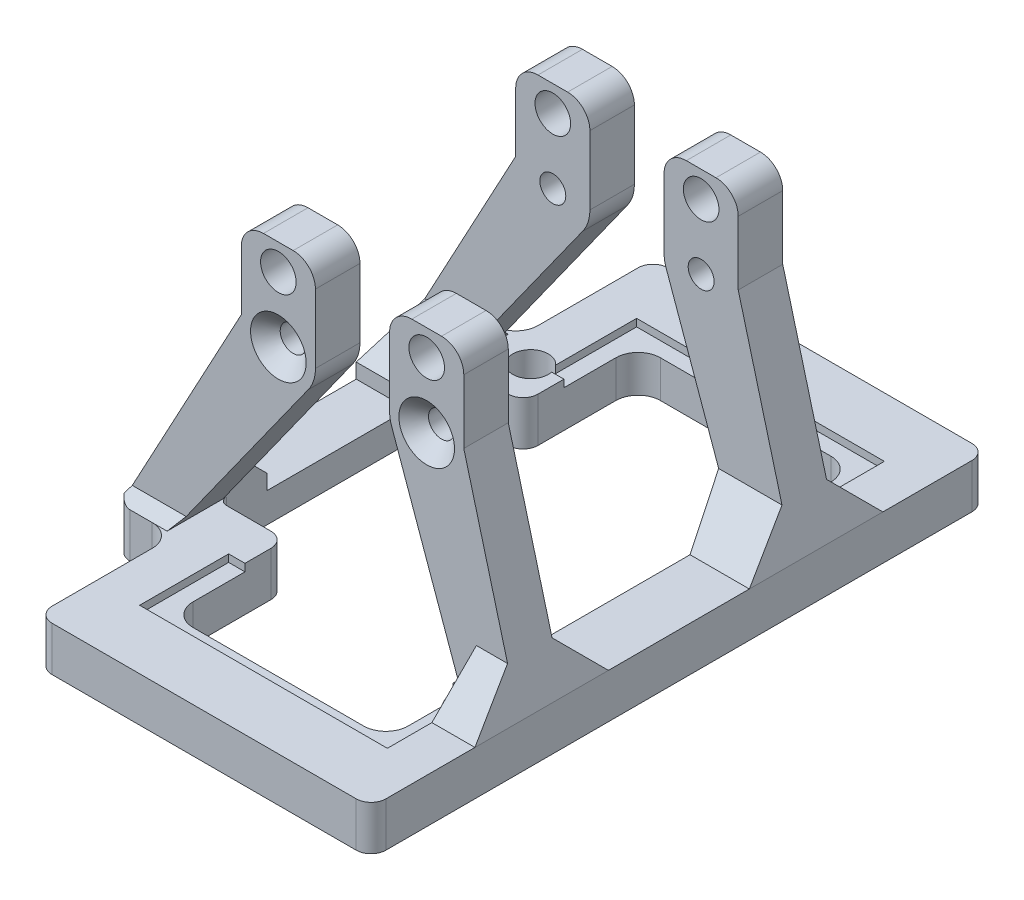
SolidWorks part; units mm, degrees
ref_plane "前视基准面" through (0, 0, 0) normal (0, 0, 1) x (1, 0, 0)
ref_plane "上视基准面" through (0, 0, 0) normal (0, 1, 0) x (1, 0, 0)
ref_plane "右视基准面" through (0, 0, 0) normal (1, 0, 0) x (0, 0, -1)
other "Configuration Table"
sketch "草图1" plane through (0, 0, 0) normal (0, 1, 0) x (1, 0, 0)
  line L0 (0, -76) -> (0, -106)
  line L1 (0, 0) -> (45, 0)
  line L2 (0, 0) -> (0, -30)
  line L3 (0, -106) -> (45, -106)
  line L4 (45, 0) -> (45, -106)
  line L5 (8, -21.5) -> (37, -21.5)
  line L6 (8, -21.5) -> (8, -37)
  line L7 (8, -84.5) -> (37, -84.5)
  line L8 (37, -21.5) -> (37, -84.5)
  line L9 (0, -30) -> (-8, -30)
  line L11 (0, -76) -> (-8, -76)
  line L12 (-8, -30) -> (-8, -76)
  line L13 (8, -69) -> (8, -84.5)
  line L14 (8, -37) -> (-1, -37)
  line L16 (8, -69) -> (-1, -69)
  line L17 (-1, -37) -> (-1, -69)
  circle A0 centre (4, -32) radius 1.75
  circle A1 centre (41, -74) radius 1.75
  dimension "D8" = 3.5
  dimension "D12" = 3.5
  dimension "D13" = 8
  dimension "D1" = 106
  dimension "D2" = 45
  dimension "D3" = 21.5
  dimension "D4" = 21.5
  dimension "D5" = 8
  dimension "D6" = 8
  dimension "D7" = 32
  dimension "D9" = 74
  dimension "D10" = 4
  dimension "D11" = 4
  dimension "D14" = 30
  dimension "D15" = 30
  dimension "D16" = 7
  dimension "D17" = 7
  dimension "D18" = 7
extrude "凸台-拉伸1" add sketch "草图1" along normal blind 6
sketch "草图3" plane through (0, 6, 0) normal (0, 1, 0) x (1, 0, 0)
  line L0 (45, -106) -> (45, 0) construction
  line L1 (0, -106) -> (45, -106)
  line L2 (0, -106) -> (0, -94.5)
  line L3 (0, -94.5) -> (45, -94.5)
  line L4 (45, -106) -> (45, -94.5)
  line L5 (37, -21.5) -> (8, -21.5) construction
  line L6 (0, 0) -> (45, 0)
  line L7 (0, 0) -> (0, -11.5)
  line L8 (0, -11.5) -> (45, -11.5)
  line L9 (45, 0) -> (45, -11.5)
  line L10 (8, -84.5) -> (37, -84.5) construction
  dimension "D1" = 10
  dimension "0" = 10
extrude "切除-拉伸1" cut sketch "草图3" against normal blind 10
sketch "草图4" plane through (0, 6, 0) normal (0, 1, 0) x (1, 0, 0)
  line L0 (45, -71) -> (45, -77)
  line L1 (45, -94.5) -> (45, -11.5) construction
  arc A0 (45, -71) -> (45, -77) centre (41, -74) ccw
  circle A1 centre (41, -74) radius 1.75
  dimension "D1" = 10
extrude "凸台-拉伸3" add sketch "草图4" against normal blind 6
sketch "草图13" plane through (0, 6, 0) normal (0, 1, 0) x (1, 0, 0)
  circle A0 centre (41, -74) radius 1.75
extrude "凸台-拉伸6" add sketch "草图13" against normal blind 0.5
sketch "草图14" plane through (0, 0, 0) normal (0, -1, 0) x (-1, 0, 0)
  circle A0 centre (-41, -74) radius 2.4
  dimension "D1" = 4.8
extrude "切除-拉伸8" cut sketch "草图14" against normal blind 4.5
sketch "草图15" plane through (0, 6, 0) normal (0, 1, 0) x (1, 0, 0)
  circle A0 centre (4, -32) radius 2.4
  dimension "D1" = 4.8
extrude "切除-拉伸9" cut sketch "草图15" against normal blind 4.5
ref_plane "基准面1" through (0, 0, 68.5) normal (0, 0, 1) x (1, 0, 0)
sketch "草图5" plane through (0, 0, 68.5) normal (0, 0, 1) x (1, 0, 0)
  line L0 (45, 6) -> (37.5, 34.1545)
  line L1 (37, 6) -> (27.8572, 31.6442)
  line L3 (-8, 6) -> (7.5, 34.7615)
  line L4 (-1, 6) -> (16.5, 30.5)
  line L5 (13.5784, 30.5) -> (17.5, 30.5) construction
  line L6 (-8, 6) -> (-1, 6)
  line L7 (37, 6) -> (45, 6)
  line L8 (37.5, 48.5) -> (37.5, 30.9) construction
  line L14 (27.5, 33.5) -> (27.5, 45.7615)
  line L15 (27.5, 45.7615) -> (37.5, 45.7615)
  line L16 (37.5, 34.1453) -> (37.5, 45.7615)
  line L17 (17.5, 23.9) -> (17.5, 48.5) construction
  line L19 (7.5, 34.7615) -> (7.5, 45.7615)
  line L20 (7.5, 45.7615) -> (17.5, 45.7615)
  line L21 (17.5, 33.5) -> (17.5, 45.7615)
  arc A0 (27.5, 33.5) -> (27.8572, 31.6442) centre (32.5, 33.5) ccw
  arc A2 (16.5, 30.5) -> (17.5, 33.5) centre (12.5, 33.5) ccw
  dimension "D1" = 11
  dimension "D2" = 10
  dimension "D3" = 0
extrude "凸台-拉伸4" add sketch "草图5" along normal blind 6 and the other way blind 37 contours L3 L6 L4 | A0 L1 L7 L0 | L0 A0 L1 region at (35.2194, 26.634, 68.5) region at (7.2781, 26.9278, 68.5)
sketch "草图11" plane through (0, 6, 0) normal (0, 1, 0) x (1, 0, 0)
  line L0 (-8, -31.5) -> (-8, -74.5) construction
  line L1 (-8, -37.5) -> (45, -37.5)
  line L2 (-8, -37.5) -> (-8, -68.5)
  line L3 (-8, -68.5) -> (45, -68.5)
  line L4 (45, -37.5) -> (45, -68.5)
  line L5 (45, -31.5) -> (45, -74.5) construction
  line L6 (-8, -74.5) -> (-1, -74.5) construction
  line L7 (-8, -31.5) -> (-1, -31.5) construction
  dimension "D1" = 6
  dimension "D2" = 6
extrude "切除-拉伸6" cut sketch "草图11" along normal through all
sketch "草图7" plane through (0, 0, 74.5) normal (0, 0, 1) x (1, 0, 0)
  circle A0 centre (12.5, 33.5) radius 1.75
  circle A1 centre (32.5, 33.5) radius 1.75
  dimension "D1" = 3.5
  dimension "D2" = 3.5
extrude "切除-拉伸2" cut sketch "草图7" against normal through all
chamfer "倒角5" distance 6 angle 45 6 edges at (41, 6, 37.5) (41, 6, 68.5) (-4.5, 6, 68.5) (-4.5, 6, 37.5) (41, 6, 74.5) (41, 6, 31.5)
chamfer "倒角7" distance 1.5 angle 45 2 edges at (-4.5, 6, 31.5) (-4.5, 6, 74.5)
sketch "草图12" plane through (0, 0, 0) normal (0, -1, 0) x (1, 0, 0)
  line L0 (3.2857, 68.5) -> (16.5, 68.5) construction
  line L1 (14.3746, 68.5) -> (-1, 68.5)
  line L2 (14.3746, 68.5) -> (14.3746, 37.5)
  line L3 (14.3746, 37.5) -> (-1, 37.5)
  line L4 (-1, 68.5) -> (-1, 37.5)
  line L5 (16.5, 37.5) -> (3.2857, 37.5) construction
  line L6 (-1, 37) -> (-1, 69) construction
  dimension "D1" = 0
extrude "切除-拉伸7" cut sketch "草图12" against normal through all
fillet "圆角6" radius 1 2 edges at (-1, 3, 37) (-1, 3, 69)
fillet "圆角1" radius 3 6 edges at (0, 3, 30) (0, 3, 76) (8, 3, 84.5) (37, 3, 84.5) (37, 3, 21.5) (8, 3, 21.5)
fillet "圆角2" radius 2 8 edges at (-8, 3, 76) (-8, 3, 30) (0, 3, 11.5) (45, 3, 11.5) (45, 3, 94.5) (0, 3, 94.5) (8, 3, 37) (8, 3, 69)
sketch "草图16" plane through (0, 0, 74.5) normal (0, 0, 1) x (1, 0, 0)
  line L0 (7.5, 45.7615) -> (17.5, 45.7615) construction
  line L1 (27.5, 45.7615) -> (37.5, 45.7615) construction
  circle A0 centre (12.5, 42.2615) radius 2.4
  circle A1 centre (32.5, 42.2615) radius 2.4
  dimension "D3" = 4.8
  dimension "D4" = 4.8
  dimension "D1" = 3.5
  dimension "D2" = 3.5
extrude "切除-拉伸10" cut sketch "草图16" against normal through all
fillet "圆角7" radius 3 8 edges at (37.5, 45.7615, 71.5) (27.5, 45.7615, 71.5) (17.5, 45.7615, 71.5) (7.5, 45.7615, 71.5) (37.5, 45.7615, 34.5) (27.5, 45.7615, 34.5) (17.5, 45.7615, 34.5) (7.5, 45.7615, 34.5)
sketch "草图17" plane through (0, 6, 0) normal (0, 1, 0) x (1, 0, 0)
  line L0 (8, -71) -> (8, -81.5) construction
  line L1 (5.8, -19.5) -> (39.2, -19.5)
  line L2 (5.8, -19.5) -> (5.8, -31.5)
  line L3 (5.8, -31.5) -> (39.2, -31.5)
  line L4 (39.2, -19.5) -> (39.2, -31.5)
  line L5 (5.8, -86.5) -> (39.2, -86.5)
  line L6 (5.8, -86.5) -> (5.8, -74.5)
  line L7 (5.8, -74.5) -> (39.2, -74.5)
  line L8 (39.2, -86.5) -> (39.2, -74.5)
  line L9 (37, -80.5) -> (37, -77) construction
  line L10 (11, -84.5) -> (34, -84.5) construction
  line L11 (8, -24.5) -> (8, -35) construction
  line L12 (37, -43.5) -> (37, -25.5) construction
  line L13 (34, -21.5) -> (11, -21.5) construction
  dimension "D1" = 2.2
  dimension "D2" = 2.2
  dimension "D3" = 2
  dimension "D4" = 12
  dimension "D5" = 2.2
  dimension "D6" = 2.2
  dimension "D7" = 2
  dimension "D8" = 12
extrude "切除-拉伸11" cut sketch "草图17" along normal through all and the other way blind 1
sketch "草图18" plane through (0, 6, 0) normal (0, 1, 0) x (1, 0, 0)
  line L1 (-8, -43.5) -> (-1, -43.5)
  line L2 (-8, -43.5) -> (-8, -62.5)
  line L3 (-8, -62.5) -> (-1, -62.5)
  line L4 (-1, -43.5) -> (-1, -62.5)
extrude "切除-拉伸12" cut sketch "草图18" against normal blind 2
chamfer "倒角8" distance 2 angle 45 4 edges at (34.25, 33.5, 74.5) (14.25, 33.5, 74.5) (14.25, 33.5, 31.5) (34.25, 33.5, 31.5)
